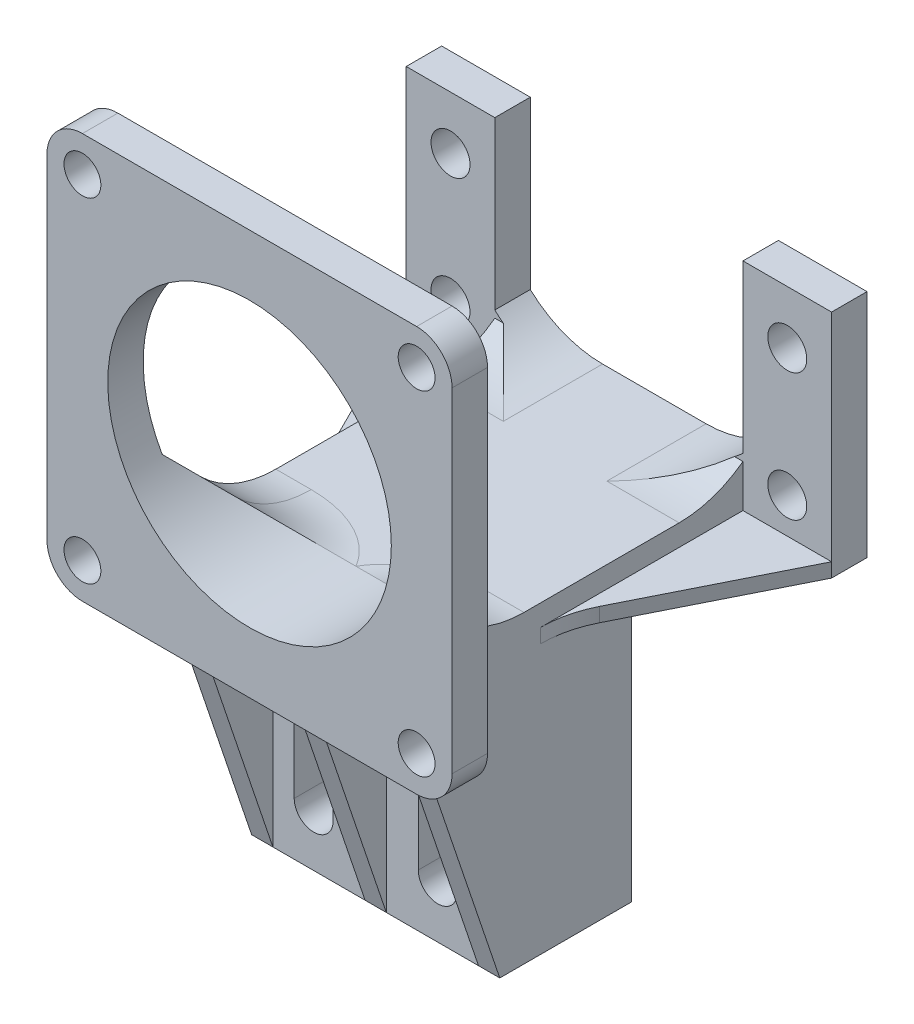
SolidWorks part; units mm, degrees
note: The reader was unsure of these and kept them because the rebuilt part matched: shared geometry of "Sketch7<2>", "Sketch7<3>".
ref_plane "Front Plane" through (0, 0, 0) normal (0, 0, 1) x (1, 0, 0)
ref_plane "Top Plane" through (0, 0, 0) normal (0, 1, 0) x (1, 0, 0)
ref_plane "Right Plane" through (0, 0, 0) normal (1, 0, 0) x (0, 0, -1)
sketch "Sketch1" plane through (0, 0, 0) normal (0, 0, 1) x (1, 0, 0)
  line L1 (-23.57, 23.57) -> (23.57, 23.57) construction
  line L2 (-23.57, 23.57) -> (-23.57, -23.57) construction
  line L3 (-23.57, -23.57) -> (23.57, -23.57) construction
  line L4 (23.57, 23.57) -> (23.57, -23.57) construction
  line L5 (-23.57, 23.57) -> (23.57, -23.57) construction
  line L6 (-23.57, -23.57) -> (23.57, 23.57) construction
  line L7 (-28.57, 28.57) -> (28.57, 28.57)
  line L8 (-28.57, 28.57) -> (-28.57, -28.57)
  line L9 (-28.57, -28.57) -> (28.57, -28.57)
  line L10 (28.57, 28.57) -> (28.57, -28.57)
  line L11 (-28.57, 28.57) -> (28.57, -28.57) construction
  line L12 (-28.57, -28.57) -> (28.57, 28.57) construction
  circle A0 centre (-23.57, 23.57) radius 2.6
  circle A1 centre (23.57, 23.57) radius 2.6
  circle A2 centre (23.57, -23.57) radius 2.6
  circle A3 centre (-23.57, -23.57) radius 2.6
  circle A4 centre (0, 0) radius 20
  point P0 (0, 0)
  point P10 (0, 0)
  dimension "D2" = 5.2
  dimension "D3" = 5
  dimension "D5" = 40
  dimension "D1" = 47.14
  dimension "D4" = 5
extrude "Boss-Extrude1" add sketch "Sketch1" along normal blind 5
sketch "Sketch2" plane through (0, 0, 0) normal (0, 0, 1) x (1, 0, 0)
  line L0 (-28.57, -28.57) -> (28.57, -28.57) construction
  line L2 (-17.5, -20) -> (-17.5, -25)
  line L3 (-17.5, -25) -> (17.5, -25)
  line L4 (17.5, -20) -> (17.5, -25)
  line L5 (0, -10.2264) -> (0, 1.4223) construction
  line L6 (-17.5, -20) -> (17.5, -20)
  circle A4 centre (0, 0) radius 20 construction
  circle A5 centre (0, 0) radius 20
  dimension "D1" = 3.57
  dimension "D2" = 8.57
  dimension "D3" = 35
extrude "Boss-Extrude2" add sketch "Sketch2" against normal blind 52.1
sketch "Sketch3" plane through (0, 0, -52.1) normal (0, 0, -1) x (-1, 0, 0)
  line L1 (-17.5, -25) -> (-30, -25)
  line L2 (-17.5, -25) -> (-17.5, 7.5)
  line L3 (-17.5, 7.5) -> (-30, 7.5)
  line L4 (-30, -25) -> (-30, 7.5)
  line L5 (17.5, -25) -> (30, -25)
  line L6 (17.5, -25) -> (17.5, 7.5)
  line L7 (17.5, 7.5) -> (30, 7.5)
  line L8 (30, -25) -> (30, 7.5)
  circle A0 centre (-23.75, -18) radius 2.75
  circle A1 centre (-23.75, 0) radius 2.75
  circle A2 centre (23.75, 0) radius 2.75
  circle A3 centre (23.75, -18) radius 2.75
  point P24 (-23.75, -25)
  point P26 (23.75, -25)
  dimension "D3" = 5.5
  dimension "D1" = 32.5
  dimension "D2" = 12.5
  dimension "D4" = 7
  dimension "D5" = 18
extrude "Boss-Extrude3" add sketch "Sketch3" against normal blind 5
sketch "Sketch4" plane through (0, -25, 0) normal (0, -1, 0) x (1, 0, 0)
  line L0 (-17.5, -47.1) -> (-17.5, 0) construction
  line L1 (-17.5, -31.41) -> (17.5, -31.41)
  line L2 (-17.5, -31.41) -> (-17.5, -12.8)
  line L3 (-17.5, -12.8) -> (17.5, -12.8)
  line L4 (17.5, -31.41) -> (17.5, -12.8)
  line L5 (17.5, -47.1) -> (17.5, 0) construction
  line L6 (-17.5, 0) -> (17.5, 0) construction
  dimension "D1" = 18.61
  dimension "D2" = 31.41
extrude "Boss-Extrude4" add sketch "Sketch4" along normal blind 37.95
sketch "Sketch5" plane through (0, 0, -12.8) normal (0, 0, 1) x (1, 0, 0)
  line L0 (17.5, -62.95) -> (17.5, -25) construction
  line L1 (-17.5, -62.95) -> (17.5, -62.95) construction
  line L2 (-17.5, -62.95) -> (-17.5, -24.85) construction
  line L3 (-17.5, -24.85) -> (17.5, -24.85) construction
  line L4 (17.5, -62.95) -> (17.5, -24.85) construction
  line L5 (-8.75, -36.01) -> (-8.75, -55.51) construction
  line L6 (-6, -36.01) -> (-6, -55.51)
  line L7 (-11.5, -36.01) -> (-11.5, -55.51)
  line L8 (8.75, -36.01) -> (8.75, -55.51) construction
  line L9 (11.5, -36.01) -> (11.5, -55.51)
  line L10 (6, -36.01) -> (6, -55.51)
  line L11 (0, -7.924) -> (0, 10.1444) construction
  arc A0 (-6, -36.01) -> (-11.5, -36.01) centre (-8.75, -36.01) ccw
  arc A1 (-11.5, -55.51) -> (-6, -55.51) centre (-8.75, -55.51) ccw
  arc A2 (11.5, -36.01) -> (6, -36.01) centre (8.75, -36.01) ccw
  arc A3 (6, -55.51) -> (11.5, -55.51) centre (8.75, -55.51) ccw
  point P9 (-8.75, -45.76)
  point P14 (8.75, -45.76)
  dimension "D3" = 25
  dimension "D1" = 38.1
  dimension "D2" = 5.5
  dimension "D4" = 17.19
  dimension "D5" = 8.75
extrude "Cut-Extrude1" cut sketch "Sketch5" against normal up to next
sketch "Sketch6" plane through (0, -25, 0) normal (0, -1, 0) x (1, 0, 0)
  line L0 (-30, -47.1) -> (-17.5, -22.1)
  line L1 (-17.5, -47.1) -> (-17.5, -31.41) construction
  line L2 (-17.5, -22.1) -> (-17.5, -47.1)
  line L3 (-17.5, -47.1) -> (-30, -47.1) construction
  line L4 (-17.5, -47.1) -> (-30, -47.1)
  line L5 (0, -54.8776) -> (0, -44.3534) construction
  line L7 (17.5, -22.1) -> (17.5, -47.1)
  line L8 (30, -47.1) -> (17.5, -22.1)
  line L9 (17.5, -47.1) -> (30, -47.1)
  dimension "D1" = 25
extrude "Boss-Extrude5" add sketch "Sketch6" against normal blind 2
sketch "Sketch7" plane through (-17.5, 0, 0) normal (-1, 0, 0) x (0, 0, 1)
  line L0 (0, -25) -> (-12.8, -62.95)
  line L1 (-12.8, -62.95) -> (-12.8, -25)
  line L2 (-12.8, -25) -> (0, -25)
chamfer "Chamfer1" distance 4 angle 45 2 edges at (17.5, -20, -49.6) (-17.5, -20, -49.6)
chamfer "Chamfer2" distance 3 angle 45 2 edges at (15.5, -20, -47.1) (-15.5, -20, -47.1)
chamfer "Chamfer4" distance 10 angle 45 2 edges at (-8.75, -20, 0) (8.75, -20, 0)
fillet "Fillet1" radius 15 2 edges at (17.5, -24, -22.1) (-17.5, -24, -22.1)
fillet "Fillet2" radius 15 4 edges at (-15.5, -20, -44.1) (-13.5, -20, -48.1) (15.5, -20, -44.1) (13.5, -20, -48.1)
fillet "Fillet3" radius 15 2 edges at (-8.75, -20, -10) (8.75, -20, -10)
fillet "Fillet6" radius 5 4 edges at (28.57, -28.57, 2.5) (-28.57, -28.57, 2.5) (-28.57, 28.57, 2.5) (28.57, 28.57, 2.5)
extrude "Boss-Extrude6" add sketch "Sketch7" against normal blind 3
extrude "Boss-Extrude7" add sketch "Sketch7<2>" along normal mid plane 3 from offset 17.5 offset against normal yes
sketch "Sketch7<2>" plane through (-17.5, 0, 0) normal (-1, 0, 0) x (0, 0, 1) same geometry as "Sketch7"
extrude "Boss-Extrude8" add sketch "Sketch7<3>" along normal blind 3 from surface at -35 starting at face at (17.5, -27.4071, -21.4972)
sketch "Sketch7<3>" plane through (-17.5, 0, 0) normal (-1, 0, 0) x (0, 0, 1) same geometry as "Sketch7"
chamfer "Chamfer5" distance 4 angle 45 2 edges at (-8, -25, -12.8) (8, -25, -12.8)
